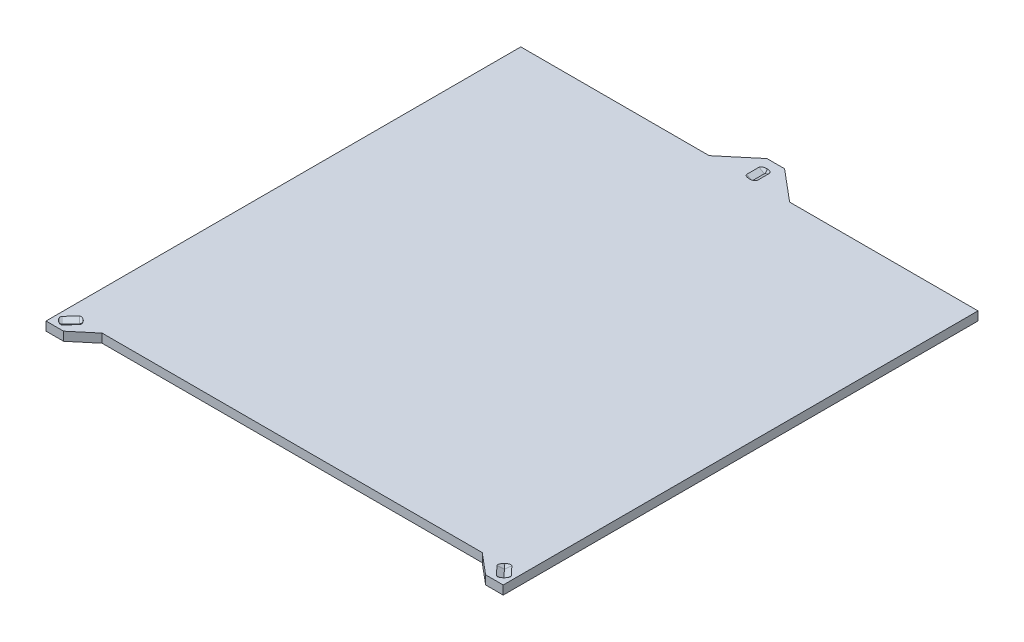
SolidWorks part; units mm, degrees
material "1060 Alloy"
ref_plane "Front Plane" through (0, 0, 0) normal (0, 0, 1) x (1, 0, 0)
ref_plane "Top Plane" through (0, 0, 0) normal (0, 1, 0) x (1, 0, 0)
ref_plane "Right Plane" through (0, 0, 0) normal (1, 0, 0) x (0, 0, -1)
sketch "Sketch1" plane through (0, 0, 0) normal (0, 1, 0) x (1, 0, 0)
  line L0 (-260, -260) -> (-260, -280)
  line L1 (260, 260) -> (45.7526, 260)
  line L2 (260, 260) -> (260, -260)
  line L3 (216.1649, -260) -> (-216.1649, -260)
  line L4 (-260, 260) -> (-260, -260)
  line L5 (260, 260) -> (-260, -260) construction
  line L6 (260, -260) -> (-260, 260) construction
  line L7 (-260, -280) -> (-240, -280)
  line L8 (-240, -280) -> (-216.1649, -260)
  line L9 (260, -260) -> (260, -280)
  line L10 (260, -280) -> (240, -280)
  line L11 (240, -280) -> (216.1649, -260)
  line L12 (0, 270) -> (0, 314.3126) construction
  line L13 (-45.7526, 260) -> (-10, 290)
  line L14 (-10, 290) -> (10, 290)
  line L15 (10, 290) -> (45.7526, 260)
  line L16 (-45.7526, 260) -> (-260, 260)
  line L17 (0, 0) -> (0, 290) construction
  point P0 (0, 0)
  dimension "D1" = 520
  dimension "D2" = 520
  dimension "D3" = 20
  dimension "D4" = 20
  dimension "D5" = 40
  dimension "D6" = 520
  dimension "D7" = 20
  dimension "D8" = 40
  dimension "D9" = 520
  dimension "D10" = 30
  dimension "D11" = 20
  dimension "D12" = 10
  dimension "D13" = 40
  dimension "D14" = 40
extrude "Boss-Extrude1" add sketch "Sketch1" along normal blind 10
ref_axis "Axis1" through (0, 10.5, 0) along (0, -1, 0)
ref_plane "Plane2" through (0, 0, 0) normal (-0.7328, 0, -0.6805) x (-0.6805, 0, 0.7328)
ref_plane "Plane3" through (-260, 0, 280) normal (0.6805, 0, -0.7328) x (0, -1, 0)
ref_plane "Plane4" through (-253.1955, 0, 272.6721) normal (0.6805, 0, -0.7328) x (0, -1, 0)
sketch "Sketch5" plane through (-253.1955, 0, 272.6721) normal (0.6805, 0, -0.7328) x (0, -1, 0)
  line L0 (-10, -13.609) -> (-10, 143.3901) construction
  line L2 (-10, 6) -> (-10, -6)
  line L3 (-10, 6) -> (-6.5359, 0)
  line L4 (-6.5359, 0) -> (-10, -6)
  line L5 (-10.5, 0) -> (0.5, 0) construction
  dimension "D1" = 30
  dimension "D2" = 30
  dimension "D3" = 12
extrude "Cut-Extrude1" cut sketch "Sketch5" along normal blind 20
fillet "Fillet1" radius 3 4 edges at (-241.7848, 8.2679, 255.9748) (-237.3881, 8.2679, 260.0575) (-250.9971, 8.2679, 274.7134) (-255.3939, 8.2679, 270.6307)
ref_plane "Plane5" through (-246.391, 0, 265.3441) normal (0.6805, 0, -0.7328) x (0, -1, 0)
mirror "Mirror1" about plane through (0, 0, 0) normal (1, 0, 0) of "Fillet1", "Cut-Extrude1"
ref_plane "Plane6" through (0, 0, -280) normal (0, 0, -1) x (-1, 0, 0)
sketch "Sketch6" plane through (0, 0, -280) normal (0, 0, -1) x (-1, 0, 0)
  line L0 (-10, 10) -> (10, 10) construction
  line L1 (0, 10.5) -> (0, -0.5) construction
  line L2 (-6, 10) -> (6, 10)
  line L3 (6, 10) -> (0, 6.5359)
  line L4 (0, 6.5359) -> (-6, 10)
  dimension "D1" = 12
  dimension "D2" = 30
  dimension "D3" = 30
extrude "Cut-Extrude2" cut sketch "Sketch6" against normal blind 20
fillet "Fillet2" radius 3 4 edges at (3, 8.2679, -260) (-3, 8.2679, -260) (3, 8.2679, -280) (-3, 8.2679, -280)
ref_axis "Axis2" through (-246.391, -0.5, 265.3441) along (0, 1, 0)
ref_plane "Plane7" through (251.1541, 0, 270.4737) normal (0.6805, 0, 0.7328) x (0.7328, 0, -0.6805)
ref_plane "Plane8" through (246.391, 0, 265.3441) normal (0.6805, 0, 0.7328) x (0.7328, 0, -0.6805)
ref_plane "Plane9" through (0, 0, 0) normal (-0.7328, 0, 0.6805) x (0.6805, 0, 0.7328)
ref_axis "Axis3" through (246.391, 10.1732, 265.3441) along (0, -1, 0)
ref_plane "Plane10" through (0, 0, -263) normal (0, 0, 1) x (1, 0, 0)
ref_plane "Plane11" through (0, 0, -270) normal (0, 0, 1) x (1, 0, 0)
ref_axis "Axis4" through (0, 10.5, -270) along (0, -1, 0)
sketch "Sketch7" plane through (0, 0, 0) normal (0, -1, 0) x (1, 0, 0)
  line L0 (247.7871, 264.0477) -> (244.9948, 266.6406) construction
  circle A0 centre (-246.391, 265.3441) radius 6.25
  circle A1 centre (246.391, 265.3441) radius 6.25
  circle A2 centre (0, -270) radius 6.25
  dimension "D1" = 12.5
  dimension "D2" = 12.5
  dimension "D3" = 12.5
extrude "Cut-Extrude3" cut sketch "Sketch7" against normal blind 5.5
